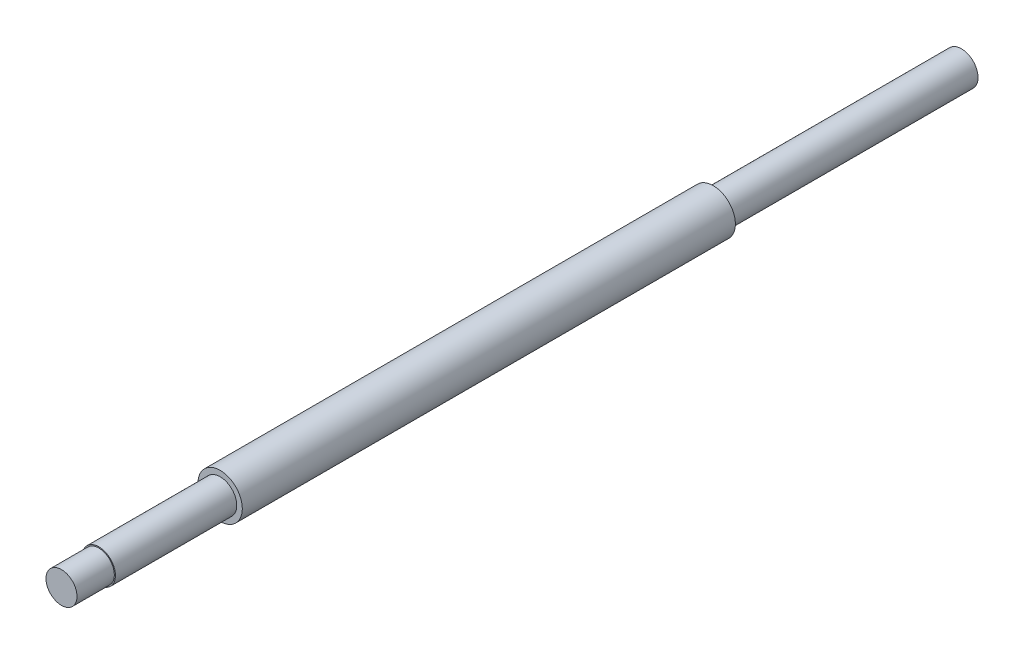
SolidWorks part; units mm, degrees
material "AISI 1020"
ref_plane "Front Plane" through (0, 0, 0) normal (0, 0, 1) x (1, 0, 0)
ref_plane "Top Plane" through (0, 0, 0) normal (0, 1, 0) x (1, 0, 0)
ref_plane "Right Plane" through (0, 0, 0) normal (1, 0, 0) x (0, 0, -1)
sketch "Sketch1" plane through (0, 0, 0) normal (0, 0, 1) x (1, 0, 0)
  circle A0 centre (0, 0) radius 6.35
  dimension "D1" = 12.7
extrude "Boss-Extrude1" add sketch "Sketch1" along normal blind 141.2875
sketch "Sketch2" plane through (0, 0, 141.2875) normal (0, 0, 1) x (1, 0, 0)
  circle A0 centre (0, 0) radius 4.7625
  dimension "D1" = 9.525
extrude "Boss-Extrude2" add sketch "Sketch2" along normal blind 45.466
sketch "Sketch3" plane through (0, 0, 0) normal (0, 0, -1) x (-1, 0, 0)
  circle A0 centre (0, 0) radius 4.7625
  dimension "D1" = 9.525
extrude "Boss-Extrude3" add sketch "Sketch3" along normal blind 71.12
sketch "Sketch4" plane through (0, 0, 0) normal (0, 1, 0) x (1, 0, 0)
  line L0 (4.7625, -186.7535) -> (4.7625, -176.0537)
  line L1 (52.578, -176.0537) -> (-52.578, -176.0537) construction
  line L2 (4.7625, -186.7535) -> (4.7625, -141.2875) construction
  line L3 (4.7625, -176.0537) -> (4.445, -176.0537)
  line L4 (4.445, -176.0537) -> (4.445, -186.7535)
  line L5 (-4.7625, -186.7535) -> (4.7625, -186.7535) construction
  line L6 (4.445, -186.7535) -> (4.7625, -186.7535)
  line L7 (0, -186.7535) -> (0, -171.0494) construction
  line L8 (0, -146.88) -> (0, -215.9928) construction
  dimension "D1" = 8.89
revolve "Cut-Revolve1" cut sketch "Sketch4" angle 360 about L7
